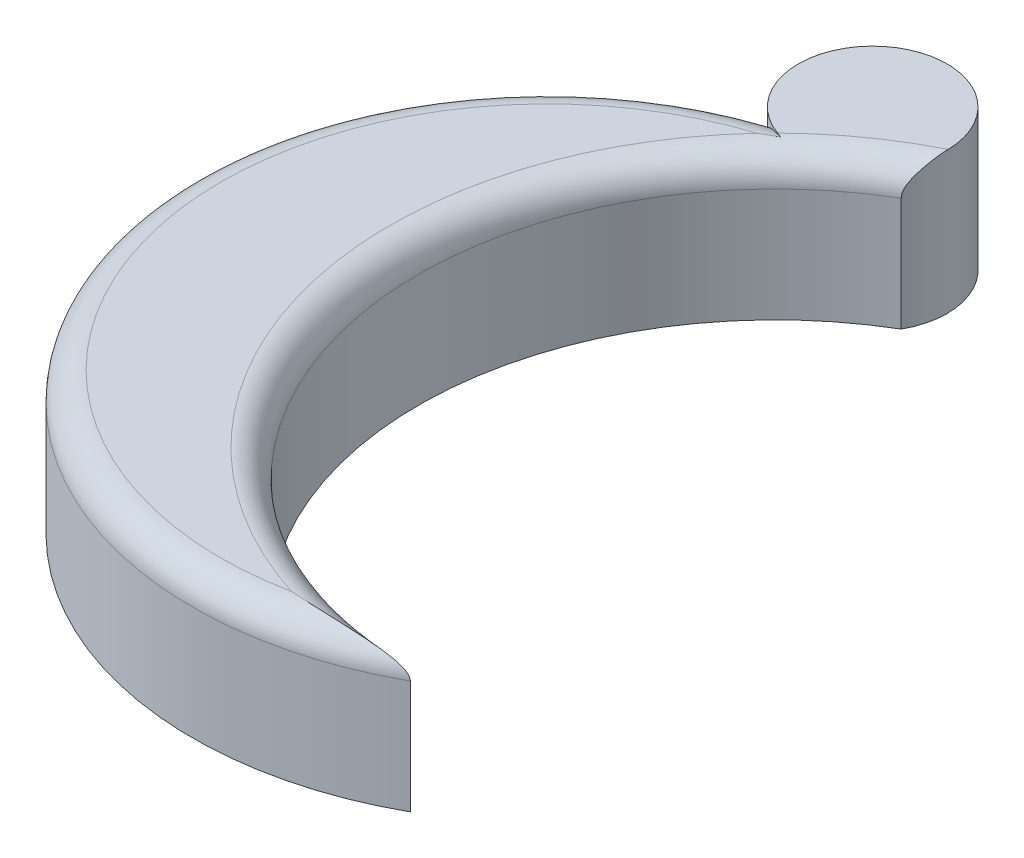
SolidWorks part; units mm, degrees
ref_plane "Alzado" through (0, 0, 0) normal (0, 0, 1) x (1, 0, 0)
ref_plane "Planta" through (0, 0, 0) normal (0, 1, 0) x (1, 0, 0)
ref_plane "Vista lateral" through (0, 0, 0) normal (1, 0, 0) x (0, 0, -1)
sketch "Croquis1" plane through (0, 0, 0) normal (0, 1, 0) x (1, 0, 0)
  arc A0 (-61.8836, 14.5759) -> (-53.7732, -3.6177) centre (-58.6468, 5.1142) ccw
  arc A1 (-58.6468, 15.1142) -> (-53.7732, -3.6177) centre (-53.534, 6.4445) ccw
  arc A2 (-58.6468, 15.1142) -> (-61.8836, 14.5759) centre (-60.481, 16.1426) ccw
  circle A3 centre (-60.481, 16.1426) radius 0.7
extrude "Saliente-Extruir1" add sketch "Croquis1" along normal blind 4 contours A1 A0 A2
fillet "Redondeo6" radius 0.8 2 edges at (-67.7804, 4, -1.0426) (-63.2748, 4, -3.9101)
ref_plane "Plano1" through (-51.2455, 0, 13.333) normal (0.9678, 0, -0.2518) x (-0.2518, 0, -0.9678)
